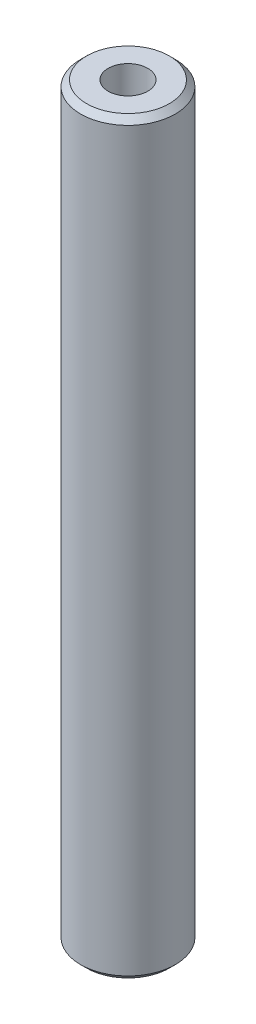
SolidWorks part; units mm, degrees
ref_plane "Front Plane" through (0, 0, 0) normal (0, 0, 1) x (1, 0, 0)
ref_plane "Top Plane" through (0, 0, 0) normal (0, 1, 0) x (1, 0, 0)
ref_plane "Right Plane" through (0, 0, 0) normal (1, 0, 0) x (0, 0, -1)
sketch "Sketch1" plane through (0, 0, 0) normal (0, 1, 0) x (1, 0, 0)
  circle A0 centre (0, 0) radius 15
  dimension "SHAFT_OD" = 30
extrude "Boss-Extrude1" add sketch "Sketch1" along normal blind 237.0732
sketch "Sketch2" plane through (0, 0, 0) normal (0, 1, 0) x (1, 0, 0)
  circle A0 centre (0, 0) radius 6.2835
  dimension "BORE_D" = 12.5669
extrude "Cut-Extrude1" cut sketch "Sketch2" along normal through all
chamfer "Chamfer1" distance 1.8993 angle 45 2 edges at (0, 237.0732, 15) (0, 0, 15)
